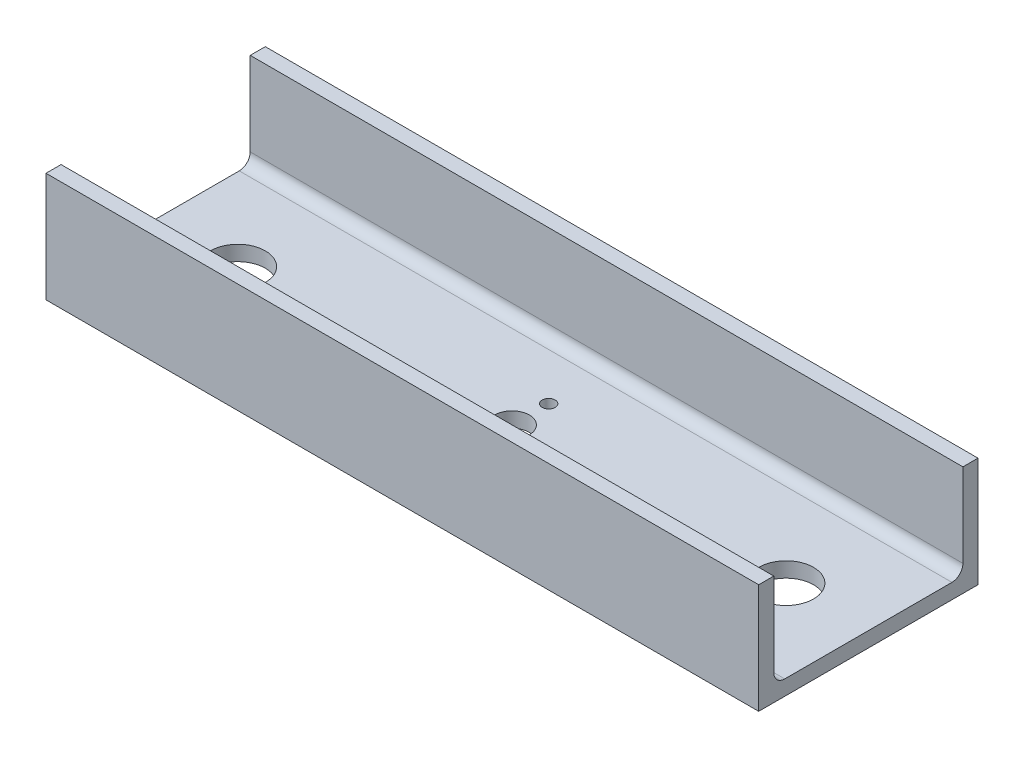
SolidWorks part; units mm, degrees
ref_plane "Front Plane" through (0, 0, 0) normal (0, 0, 1) x (1, 0, 0)
ref_plane "Top Plane" through (0, 0, 0) normal (0, 1, 0) x (1, 0, 0)
ref_plane "Right Plane" through (0, 0, 0) normal (1, 0, 0) x (0, 0, -1)
sketch "Sketch1" plane through (0, 0, 0) normal (1, 0, 0) x (0, 0, -1)
  line L0 (-21.9075, 9.2075) -> (21.9075, 9.2075)
  line L1 (-25.4, -12.7) -> (25.4, -12.7)
  line L2 (-25.4, -12.7) -> (-25.4, 12.7)
  line L3 (-25.4, 12.7) -> (25.4, 12.7)
  line L4 (25.4, -12.7) -> (25.4, 12.7)
  line L5 (-25.4, -12.7) -> (25.4, 12.7) construction
  line L6 (-25.4, 12.7) -> (25.4, -12.7) construction
  line L7 (21.9075, -6.6675) -> (21.9075, 9.2075)
  line L8 (-19.3675, -9.2075) -> (19.3675, -9.2075)
  line L9 (-21.9075, -6.6675) -> (-21.9075, 9.2075)
  line L10 (-21.9075, 9.2075) -> (-21.9075, 12.7)
  line L11 (21.9075, 9.2075) -> (21.9075, 12.7)
  line L12 (21.9075, -9.2075) -> (21.9075, 9.2075) construction
  line L13 (-21.9075, -9.2075) -> (21.9075, -9.2075) construction
  line L14 (-21.9075, -9.2075) -> (-21.9075, 9.2075) construction
  arc A0 (21.9075, -6.6675) -> (19.3675, -9.2075) centre (19.3675, -6.6675) cw
  arc A1 (-19.3675, -9.2075) -> (-21.9075, -6.6675) centre (-19.3675, -6.6675) cw
  point P0 (0, 0)
  dimension "D4" = 2.54
  dimension "D1" = 25.4
  dimension "D2" = 50.8
  dimension "D3" = 3.4925
extrude "Boss-Extrude1" add sketch "Sketch1" along normal blind 165.1 contours L8 A1 L9 L10 L3 L2 L1 L4 L11 L7 A0 region at (0, 1.27, 22.4755)
sketch "Sketch2" plane through (0, -12.7, 0) normal (0, -1, 0) x (1, 0, 0)
  line L0 (0, 0) -> (165.1, 0) construction
  line L3 (0, 25.4) -> (0, -25.4) construction
  line L4 (165.1, 25.4) -> (165.1, -25.4) construction
  line L11 (0, 0) -> (19.05, 0)
  line L12 (165.1, 0) -> (146.05, 0)
  line L13 (82.55, 8.5) -> (82.55, -8.5) construction
  circle A4 centre (19.05, 0) radius 6.35
  circle A5 centre (146.05, 0) radius 6.35
  circle A6 centre (82.55, 8.5) radius 1.5
  circle A7 centre (82.55, -8.5) radius 1.5
  circle A8 centre (82.55, 0) radius 4
  point P14 (82.55, 0)
  point P15 (82.55, 0)
  dimension "D5" = 17
  dimension "D2" = 12.7
  dimension "D4" = 12.7
  dimension "D6" = 3
  dimension "D7" = 3
  dimension "D8" = 8
  dimension "D1" = 19.05
  dimension "D3" = 19.05
extrude "Cut-Extrude1" cut sketch "Sketch2" against normal blind 11.938 contours A4 | A6 | A8 | A7 | A5 region at (19.05, -12.7, -6.1704) region at (139.8796, -12.7, 0) region at (82.55, -12.7, 8.5) region at (82.55, -12.7, -8.5) region at (82.55, -12.7, 0)
sketch "Sketch3" plane through (0, -12.7, 0) normal (0, -1, 0) x (1, 0, 0)
  line L0 (19.05, 0) -> (41.0012, 0) construction
  line L1 (41.0012, 0) -> (60.5988, 0) construction
  line L2 (50.8, 0) -> (50.8, 16.3974) construction
  line L3 (50.8, 19.5724) -> (50.8, 13.2224) construction
  line L4 (52.9, 19.5724) -> (52.9, 13.2224)
  line L5 (48.7, 19.5724) -> (48.7, 13.2224)
  line L6 (82.55, 0) -> (82.55, 25.4)
  line L7 (165.1, 25.4) -> (0, 25.4) construction
  line L8 (124.0988, 0) -> (104.5012, 0) construction
  line L9 (114.3, 0) -> (114.3, 16.3974) construction
  line L10 (114.3, 19.5724) -> (114.3, 13.2224) construction
  line L11 (112.2, 19.5724) -> (112.2, 13.2224)
  line L12 (116.4, 19.5724) -> (116.4, 13.2224)
  circle A0 centre (19.05, 0) radius 21.9512
  circle A1 centre (82.55, 0) radius 21.9512
  circle A2 centre (146.05, 0) radius 21.9512
  arc A3 (26.5015, 20.6477) -> (75.0985, 20.6477) centre (50.8, 87.9783) ccw construction
  circle A4 centre (50.8, 16.3974) radius 2.1
  arc A5 (52.9, 19.5724) -> (48.7, 19.5724) centre (50.8, 19.5724) ccw
  arc A6 (48.7, 13.2224) -> (52.9, 13.2224) centre (50.8, 13.2224) ccw
  arc A7 (138.5985, 20.6477) -> (90.0015, 20.6477) centre (114.3, 87.9783) cw construction
  arc A8 (112.2, 19.5724) -> (116.4, 19.5724) centre (114.3, 19.5724) cw
  arc A9 (116.4, 13.2224) -> (112.2, 13.2224) centre (114.3, 13.2224) cw
  point P16 (50.8, 16.3974)
  point P33 (114.3, 16.3974)
  dimension "D1" = 43.9023
  dimension "D2" = 43.9023
  dimension "D3" = 4.2
  dimension "D4" = 2.1
  dimension "D5" = 6.35
extrude "Cut-Extrude2" cut sketch "Sketch3" against normal blind 7.874 contours L4 A5 L5 A4 | A4 | L5 A6 L4 A4 | A9 L12 A8 L11 region at (50.8, -12.7, 19.6342) region at (50.8, -12.7, 16.3974) region at (50.8, -12.7, 13.1606) region at (114.3, -12.7, 16.3974)
